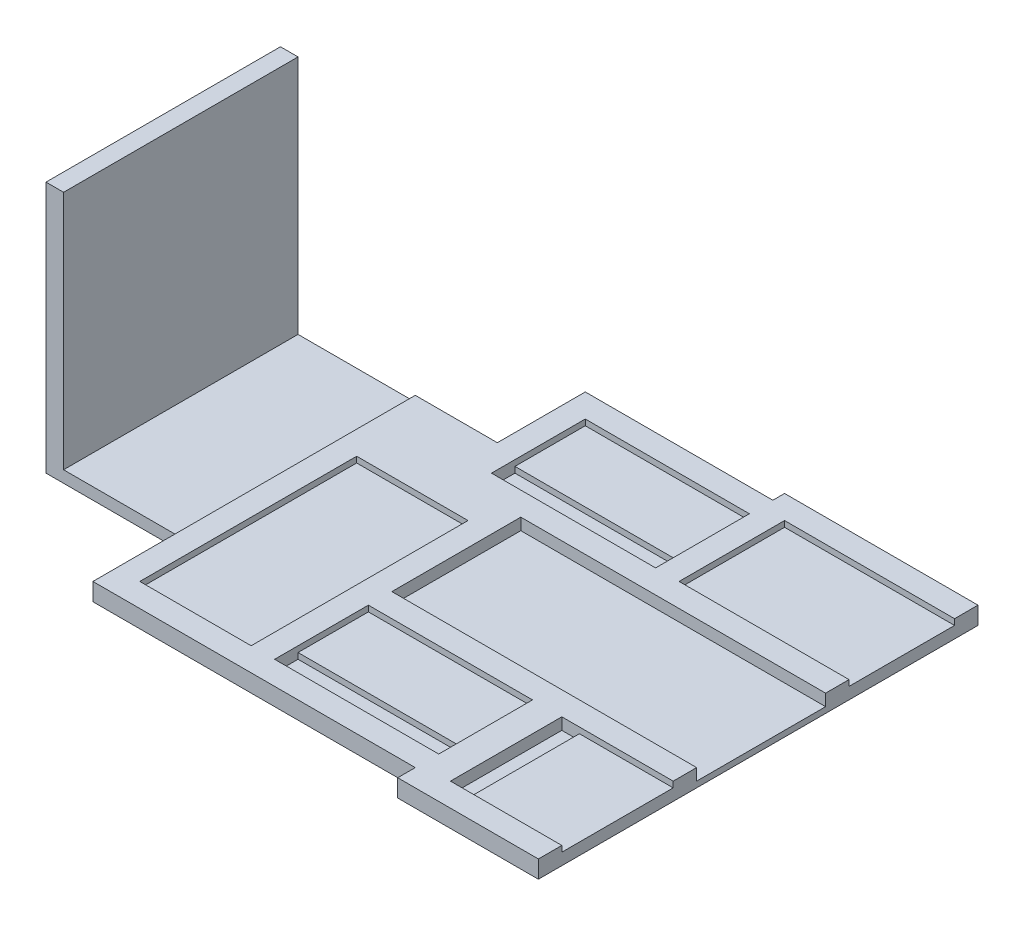
SolidWorks part; units mm, degrees
ref_plane "Plano frontal" through (0, 0, 0) normal (0, 0, 1) x (1, 0, 0)
ref_plane "Plano superior" through (0, 0, 0) normal (0, 1, 0) x (1, 0, 0)
ref_plane "Plano direito" through (0, 0, 0) normal (1, 0, 0) x (0, 0, -1)
sketch "Pico" plane through (0, 0, 0) normal (0, 1, 0) x (1, 0, 0)
  line L1 (-52, 11) -> (0, 11)
  line L2 (-52, 11) -> (-52, -11)
  line L3 (-52, -11) -> (0, -11)
  line L4 (0, 11) -> (0, -11)
  dimension "D1" = 52
  dimension "D2" = 22
sketch "SD Card" plane through (0, 0, 0) normal (0, 1, 0) x (1, 0, 0)
  line L0 (0, 11) -> (0, -11) construction
  line L1 (0, -15) -> (-19, -15)
  line L2 (0, -15) -> (0, -34)
  line L3 (0, -34) -> (-19, -34)
  line L4 (-19, -15) -> (-19, -34)
  line L5 (-52, -11) -> (0, -11) construction
  point P10 (0, 0)
  dimension "D3" = 4
  dimension "D1" = 19
  dimension "D2" = 19
sketch "Acelerometro1" plane through (0, 0, 0) normal (0, 1, 0) x (1, 0, 0)
  line L1 (-52, -15) -> (-24, -15)
  line L2 (-52, -15) -> (-52, -31)
  line L3 (-52, -31) -> (-24, -31)
  line L4 (-24, -15) -> (-24, -31)
  line L5 (-52, 11) -> (-52, -11) construction
  line L6 (0, -15) -> (-19, -15) construction
  dimension "D1" = 28
  dimension "D2" = 16
sketch "Mod. Bat" plane through (0, 0, 0) normal (0, 1, 0) x (1, 0, 0)
  line L0 (0, 11) -> (0, -11) construction
  line L1 (-29, 33) -> (0, 33)
  line L2 (-29, 33) -> (-29, 15)
  line L3 (-29, 15) -> (0, 15)
  line L4 (0, 33) -> (0, 15)
  line L5 (-52, 11) -> (0, 11) construction
  dimension "D1" = 4
  dimension "D2" = 29
  dimension "D3" = 18
sketch "step-up" plane through (0, 0, 0) normal (0, 1, 0) x (1, 0, 0)
  line L0 (-52, -31) -> (-24, -31) construction
  line L1 (-75, -31) -> (-56, -31)
  line L2 (-75, -31) -> (-75, 6)
  line L3 (-75, 6) -> (-56, 6)
  line L4 (-56, -31) -> (-56, 6)
  line L5 (-52, 11) -> (-52, -11) construction
  dimension "D3" = 4
  dimension "D1" = 19
  dimension "D2" = 37
sketch "Acelerometro2" plane through (0, 0, 0) normal (0, 1, 0) x (1, 0, 0)
  line L0 (-29, 15) -> (0, 15) construction
  line L1 (-33, 31) -> (-61, 31)
  line L2 (-33, 31) -> (-33, 15)
  line L3 (-33, 15) -> (-61, 15)
  line L4 (-61, 31) -> (-61, 15)
  line L5 (-29, 33) -> (-29, 15) construction
  point P8 (0, 0)
  dimension "D1" = 16
  dimension "D2" = 28
  dimension "D3" = 4
sketch "Sketch7" plane through (0, 0, 0) normal (0, 1, 0) x (1, 0, 0)
  line L0 (0, 11) -> (0, -11) construction
  line L1 (-75, -31) -> (-75, 6) construction
  line L2 (-52, -31) -> (-24, -31) construction
  line L3 (0, -34) -> (-19, -34) construction
  line L4 (-24, -15) -> (-24, -31) construction
  line L5 (-65, 20) -> (-102, 20)
  line L6 (-102, 20) -> (-102, -20)
  line L7 (-102, -20) -> (-79, -20)
  line L8 (0, 0) -> (20.9018, 0) construction
  line L47 (0, 37) -> (-33, 37)
  line L48 (-33, 37) -> (-33, 35)
  line L49 (-33, 35) -> (-65, 35)
  line L50 (-65, 35) -> (-65, 20)
  line L52 (-79, -20) -> (-79, -35)
  line L53 (-79, -35) -> (-24, -35)
  line L54 (-24, -35) -> (-24, -38)
  line L55 (-24, -38) -> (0, -38)
  line L56 (0, -38) -> (0, 37)
  line L57 (-33, 31) -> (-33, 15) construction
  line L58 (-29, 33) -> (0, 33) construction
  line L59 (-33, 31) -> (-61, 31) construction
  line L61 (-61, 31) -> (-61, 15) construction
  point P34 (0, 0)
  point P36 (0, 0)
  dimension "D1" = 4
  dimension "D4" = 4
  dimension "D6" = 4
  dimension "D7" = 4
  dimension "D8" = 4
  dimension "D9" = 40
  dimension "D10" = 23
extrude "Boss-Extrude2" add sketch "Sketch7" against normal blind 3 contours L5 L6 L7 L52 L53 L54 L55 L56 L47 L48 L49 L50
extrude "Cut-mod Bat" cut sketch "Mod. Bat" against normal blind 1 contours L1 L4 L3 L2
extrude "Cut-Pico" cut sketch "Pico" against normal blind 2 contours L1 L4 L3 L2
extrude "Cut-SD Card" cut sketch "SD Card" against normal blind 1 contours L4 L3 L2 L1
sketch "SD Pin " plane through (0, 0, 0) normal (0, 1, 0) x (1, 0, 0)
  line L0 (-16, -15) -> (-16, -34)
  line L1 (0, -15) -> (-19, -15) construction
  line L2 (0, -34) -> (-19, -34) construction
  line L3 (-19, -15) -> (-19, -34) construction
  line L4 (-16, -15) -> (-19, -15)
  line L5 (-19, -15) -> (-19, -34)
  line L6 (-19, -34) -> (-16, -34)
  dimension "D1" = 3
extrude "Cut-SD Pin" cut sketch "SD Pin " against normal blind 2
extrude "Cut-Acl1" cut sketch "Acelerometro1" against normal blind 1 contours L1 L4 L3 L2
extrude "Cut-StepUp" cut sketch "step-up" against normal blind 1 contours L2 L3 L4 L1
extrude "Cut-Acl2" cut sketch "Acelerometro2" against normal blind 1 contours L3 L4 L1 L2
sketch "Sketch10" plane through (0, 0, 0) normal (0, 1, 0) x (1, 0, 0)
  line L0 (-61, 31) -> (-61, 15) construction
  line L1 (-33, 15) -> (-61, 15)
  line L2 (-33, 15) -> (-33, 19)
  line L3 (-33, 19) -> (-61, 19)
  line L4 (-61, 15) -> (-61, 19)
  line L10 (-52, -15) -> (-52, -31) construction
  line L11 (-24, -31) -> (-52, -31)
  line L12 (-24, -31) -> (-24, -27)
  line L13 (-24, -27) -> (-52, -27)
  line L14 (-52, -31) -> (-52, -27)
  point P14 (0, 0)
  dimension "D1" = 4
  dimension "D2" = 4
extrude "Cut-Acl1 Pin" cut sketch "Sketch10" against normal blind 2 contours L3 L4 L1 L2
extrude "Cut-Acl2 Pin" cut sketch "Sketch10<3>" against normal blind 2 contours L13 L14 L11 L12
sketch "Sketch10<3>" plane through (0, 0, 0) normal (0, 1, 0) x (1, 0, 0) same geometry as "Sketch10"
sketch "Sketch11" plane through (0, 0, 0) normal (0, 1, 0) x (1, 0, 0)
  line L0 (-102, -20) -> (-79, -20) construction
  line L1 (-102, 20) -> (-99, 20)
  line L2 (-102, 20) -> (-102, -20)
  line L3 (-102, -20) -> (-99, -20)
  line L4 (-99, 20) -> (-99, -20)
  dimension "D1" = 3
extrude "Boss-Extrude3" add sketch "Sketch11" along normal blind 40
sketch "Sketch12" plane through (0, 0, 0) normal (0, 1, 0) x (1, 0, 0)
  line L1 (-79, -20) -> (-99, -20)
  line L2 (-79, -20) -> (-79, 20)
  line L3 (-79, 20) -> (-99, 20)
  line L4 (-99, -20) -> (-99, 20)
extrude "Cut-Extrude15" cut sketch "Sketch12" against normal blind 1
equation "\"espaco\"=4"
equation "\"D3@Acelerometro2\"=\"espaco\""
equation "\"D3@SD Card\"=\"espaco\""
equation "\"D3@step-up\"=\"espaco\""
equation "\"D1@Sketch7\"=\"espaco\""
equation "\"D2@Sketch7\"=\"espaco\""
equation "\"D4@Sketch7\"=\"espaco\""
equation "\"D6@Sketch7\"=\"espaco\""
equation "\"D7@Sketch7\"=\"espaco\""
equation "\"D8@Sketch7\"=\"espaco\""
equation "\"espessura\" = 3"
equation "\"D10@Sketch7\"=\"espessura\"+20"
equation "\"D1@Boss-Extrude2\"=\"espessura\""
equation "\"D1@Cut-mod Bat\" = 1mm"
equation "\"D1@Sketch11\"=\"espessura\""
